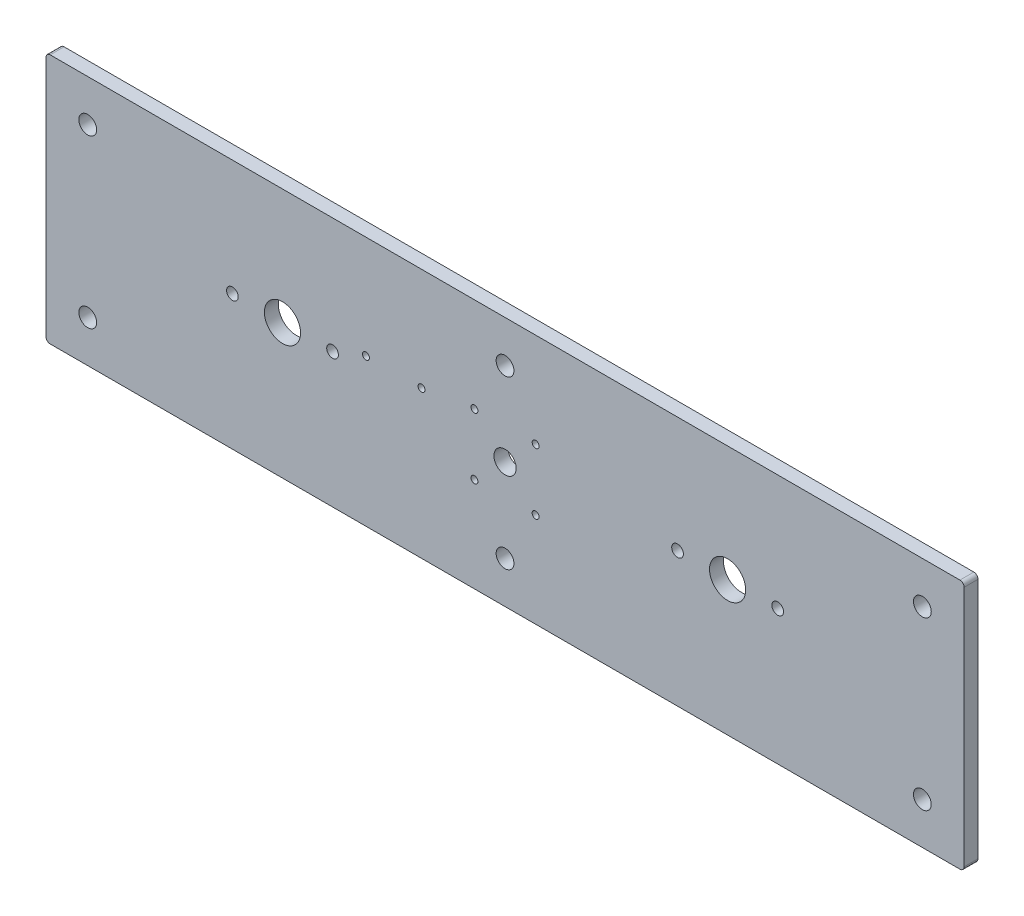
SolidWorks part; units mm, degrees
ref_plane "Front Plane" through (0, 0, 0) normal (0, 0, 1) x (1, 0, 0)
ref_plane "Top Plane" through (0, 0, 0) normal (0, 1, 0) x (1, 0, 0)
ref_plane "Right Plane" through (0, 0, 0) normal (1, 0, 0) x (0, 0, -1)
sketch "Sketch1" plane through (0, 0, 0) normal (0, 0, 1) x (1, 0, 0)
  line L1 (-165, -45) -> (165, -45)
  line L2 (-165, -45) -> (-165, 45)
  line L3 (-165, 45) -> (165, 45)
  line L4 (165, -45) -> (165, 45)
  line L5 (-165, -45) -> (165, 45) construction
  line L6 (-165, 45) -> (165, -45) construction
  point P0 (0, 0)
  dimension "D1" = 330
  dimension "D2" = 90
extrude "Boss-Extrude1" add sketch "Sketch1" along normal mid plane 5
hole_wizard "M6 Clearance Hole1" positions "Sketch6" profile "Sketch5" hole size "M6" standard "ANSI Metric"
sketch "Sketch6" plane through (0, 0, 2.5) normal (0, 0, 1) x (1, 0, 0)
  line L0 (-999.1588, 30) -> (49000.8412, 30) construction
  line L1 (-996.5045, -30) -> (49003.4955, -30) construction
  line L2 (-150, -995.3212) -> (-150, 49004.6788) construction
  line L3 (0, -1000) -> (0, 49000) construction
  line L4 (150, -1006.2702) -> (150, 48993.7298) construction
  line L5 (-165, 45) -> (-165, -45) construction
  line L6 (165, -45) -> (165, 45) construction
  line L7 (165, 45) -> (-165, 45) construction
  line L8 (-165, -45) -> (165, -45) construction
  point P27 (-150, 30)
  point P29 (-150, -30)
  point P31 (0, 30)
  point P33 (0, -30)
  point P35 (150, -30)
  point P37 (150, 30)
  dimension "D1" = 15
  dimension "D2" = 15
  dimension "D3" = 15
  dimension "D4" = 15
sketch "Sketch5" plane through (-150, 30, 2.5) normal (1, 0, 0) x (0, -1, 0)
  line L0 (0, 0) -> (0, 11.9228)
  line L1 (0, 11.9228) -> (3.2, 10)
  line L2 (3.2, 10) -> (3.2, 0)
  line L5 (3.2, 0) -> (0, 0)
  line L10 (0, 11.9228) -> (-3.2, 10) construction
  line L11 (0, -6.35) -> (0, 107.95) construction
  dimension "Hole Dia." = 6.4
  dimension "Hole Depth" = 10
  dimension "Drill Angle" = 118
sketch "Sketch3" plane through (0, 0, 2.5) normal (0, 0, 1) x (1, 0, 0)
  line L0 (-165, 3.4) -> (165, 3.4) construction
  circle A0 centre (-80, 3.4) radius 6.5
  dimension "D1" = 13
  dimension "D7" = 80
  dimension "D3" = 3.4
extrude "Cut-Extrude2" cut sketch "Sketch3" against normal through all
hole_wizard "M5x0.8 Tapped Hole1" positions "Sketch8" profile "Sketch7" tap size "M5x0.8" standard "ANSI Metric" end condition through all
sketch "Sketch8" plane through (0, 0, 2.5) normal (0, 0, 1) x (1, 0, 0)
  line L0 (-1080, 3.4) -> (48920, 3.4) construction
  circle A0 centre (-80, 3.4) radius 6.5 construction
  point P6 (-98, 3.4)
  point P8 (-62, 3.4)
  dimension "D1" = 18
  dimension "D2" = 18
sketch "Sketch7" plane through (-98, 3.4, 2.5) normal (1, 0, 0) x (0, -1, 0)
  line L0 (0, 0) -> (0, 5)
  line L1 (0, 5) -> (2.1, 5)
  line L2 (2.1, 5) -> (2.1, 0)
  line L5 (2.1, 0) -> (0, 0)
  line L11 (0, -6.35) -> (0, 107.95) construction
  dimension "Thru Tap Drill Dia." = 4.2
  dimension "Thru Tap Drill Depth" = 5
cosmetic thread "Hole Thread1" parameters "D2"=5
cosmetic thread "Hole Thread2" parameters "D2"=5
mirror "Mirror1" about plane through (0, 0, 0) normal (1, 0, 0) of "M5x0.8 Tapped Hole1", "Cut-Extrude2"
sketch "Sketch4" plane through (0, 0, 2.5) normal (0, 0, 1) x (1, 0, 0)
  circle A0 centre (0, 0) radius 4
  dimension "D1" = 8
extrude "Cut-Extrude3" cut sketch "Sketch4" against normal through all
hole_wizard "M3x0.5 Tapped Hole1" positions "Sketch10" profile "Sketch9" tap size "M3x0.5" standard "ANSI Metric" end condition through all
sketch "Sketch10" plane through (0, 0, 2.5) normal (0, 0, 1) x (1, 0, 0)
  line L1 (-11, -11) -> (11, -11) construction
  line L2 (-11, -11) -> (-11, 11) construction
  line L3 (-11, 11) -> (11, 11) construction
  line L4 (11, -11) -> (11, 11) construction
  line L5 (-11, -11) -> (11, 11) construction
  line L6 (-11, 11) -> (11, -11) construction
  point P2 (11, 11)
  point P67 (-11, -11)
  point P68 (-11, 11)
  point P69 (11, -11)
  dimension "D1" = 22
  dimension "D2" = 22
  dimension "D3" = 11
  dimension "D4" = 11
sketch "Sketch9" plane through (11, 11, 2.5) normal (1, 0, 0) x (0, -1, 0)
  line L0 (0, 0) -> (0, 5)
  line L1 (0, 5) -> (1.25, 5)
  line L2 (1.25, 5) -> (1.25, 0)
  line L5 (1.25, 0) -> (0, 0)
  line L11 (0, -6.35) -> (0, 107.95) construction
  dimension "Thru Tap Drill Dia." = 2.5
  dimension "Thru Tap Drill Depth" = 5
cosmetic thread "Hole Thread3" parameters "D2"=3
cosmetic thread "Hole Thread4" parameters "D2"=3
cosmetic thread "Hole Thread5" parameters "D2"=3
cosmetic thread "Hole Thread6" parameters "D2"=3
fillet "Fillet1" radius 1.5 4 edges at (-165, -45, 0) (-165, 45, 0) (165, -45, 0) (165, 45, 0)
hole_wizard "M3x0.5 Tapped Hole2" positions "Sketch12" profile "Sketch11" tap size "M3x0.5" standard "ANSI Metric" end condition through all
sketch "Sketch12" plane through (0, 0, 2.5) normal (0, 0, 1) x (1, 0, 0)
  line L0 (-50, 8) -> (-30, 8) construction
  point P0 (-30, 8)
  point P2 (-50, 8)
  dimension "D1" = 20
  dimension "D2" = 30
  dimension "D3" = 8
sketch "Sketch11" plane through (-30, 8, 2.5) normal (1, 0, 0) x (0, -1, 0)
  line L0 (0, 0) -> (0, 5)
  line L1 (0, 5) -> (1.25, 5)
  line L2 (1.25, 5) -> (1.25, 0)
  line L5 (1.25, 0) -> (0, 0)
  line L11 (0, -6.35) -> (0, 107.95) construction
  dimension "Thru Tap Drill Dia." = 2.5
  dimension "Thru Tap Drill Depth" = 5
cosmetic thread "Hole Thread7" parameters "D2"=3
cosmetic thread "Hole Thread8" parameters "D2"=3
